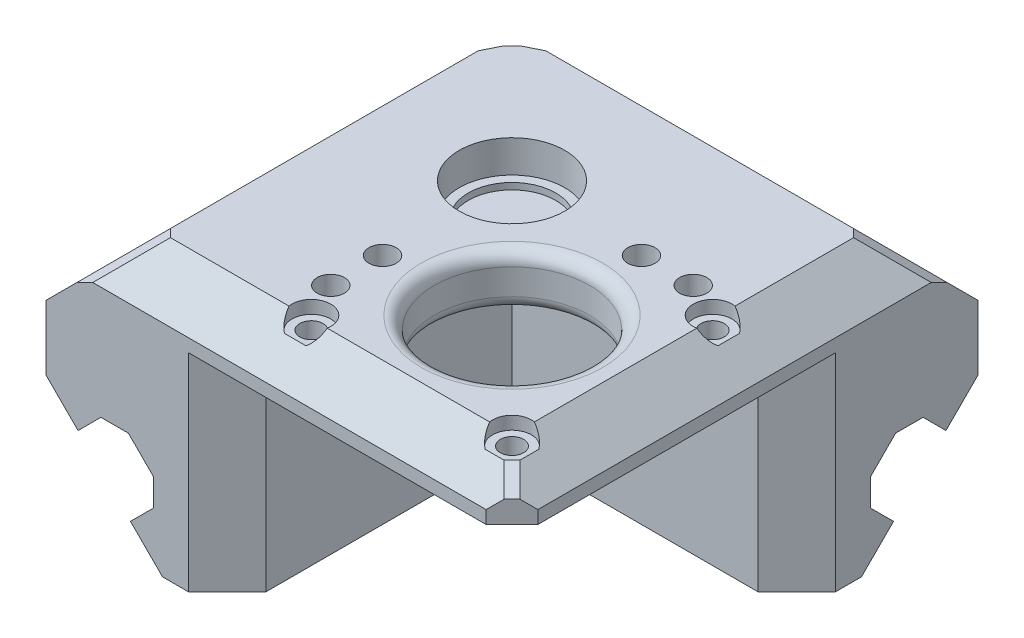
SolidWorks part; units mm, degrees
ref_plane "Front Plane" through (0, 0, 0) normal (0, 0, 1) x (1, 0, 0)
ref_plane "Top Plane" through (0, 0, 0) normal (0, 1, 0) x (1, 0, 0)
ref_plane "Right Plane" through (0, 0, 0) normal (1, 0, 0) x (0, 0, -1)
sketch "Sketch1" plane through (0, 0, 0) normal (0, 1, 0) x (1, 0, 0)
  line L1 (-36, 36) -> (36, 36)
  line L2 (-36, 36) -> (-36, -36)
  line L3 (-36, -36) -> (36, -36)
  line L4 (36, 36) -> (36, -36)
  line L5 (-36, 36) -> (36, -36) construction
  line L6 (-36, -36) -> (36, 36) construction
  circle A0 centre (14, -14) radius 12
  circle A1 centre (29.5, 1.5) radius 1.8
  circle A2 centre (29.5, -29.5) radius 1.8
  circle A3 centre (-1.5, -29.5) radius 1.8
  circle A4 centre (-1.5, 1.5) radius 1.8
  point P0 (0, 0)
  dimension "D3" = 24
  dimension "D5" = 3.6
  dimension "D1" = 72
  dimension "D2" = 72
  dimension "D4" = 22
  dimension "D6" = 31
  dimension "D7" = 15.5
extrude "Boss-Extrude1" add sketch "Sketch1" along normal blind 40
sketch "Sketch6" plane through (0, 0, 0) normal (0, -1, 0) x (-1, 0, 0)
  line L1 (-36, -36) -> (8, -36)
  line L2 (-36, -36) -> (-36, 8)
  line L3 (-36, 8) -> (8, 8)
  line L4 (8, -36) -> (8, 8)
  dimension "D1" = 44
  dimension "D2" = 44
extrude "Cut-Extrude1" cut sketch "Sketch6" against normal blind 32
chamfer "Chamfer1" distance 18 angle 45 3 edges at (-36, 20, -36) (0, 0, -36) (-36, 0, 0)
sketch "Sketch7" plane through (0, 40, 0) normal (0, 1, 0) x (1, 0, 0)
  line L1 (-18, 36) -> (-36, 36)
  line L2 (-18, 36) -> (-18, 18)
  line L3 (-18, 18) -> (-36, 18)
  line L4 (-36, 36) -> (-36, 18)
extrude "Cut-Extrude2" cut sketch "Sketch7" against normal through all
chamfer "Chamfer2" distance 8 angle 45 1 edges at (-18, 20, -18)
chamfer "Chamfer3" distance 4 angle 45 1 edges at (36, 36, 36)
sketch "Sketch8" plane through (0, 40, 0) normal (0, 1, 0) x (1, 0, 0)
  circle A0 centre (-1.5, 1.5) radius 3
  circle A1 centre (29.5, 1.5) radius 3
  circle A2 centre (29.5, -29.5) radius 3
  circle A3 centre (-1.5, -29.5) radius 3
  dimension "D1" = 6
extrude "Cut-Extrude3" cut sketch "Sketch8" against normal blind 2
chamfer "Chamfer5" distance 6 angle 45 2 edges at (36, 16, -8) (-8, 16, 36)
chamfer "Chamfer6" distance 6 angle 45 2 edges at (36, 40, -2) (-2, 40, 36)
chamfer "Chamfer7" distance 12 angle 45 2 edges at (6, 40, -36) (-36, 40, 6)
sketch "Sketch9" plane through (0, -9, -9) normal (0, -0.7071, -0.7071) x (-1, 0, 0)
  circle A0 centre (11.9774, 15.4558) radius 2.1
  circle A1 centre (-20.0226, 15.4558) radius 2.1
  circle A2 centre (-20.0226, 35.4558) radius 2.1
  circle A3 centre (11.9774, 35.4558) radius 2.1
  dimension "D1" = 4.2
extrude "Cut-Extrude4" cut sketch "Sketch9" against normal blind 6
sketch "Sketch10" plane through (-9, -9, 0) normal (-0.7071, -0.7071, 0) x (-0.7071, 0.7071, 0)
  circle A0 centre (35.4558, 12) radius 2.1
  circle A1 centre (35.4558, -20) radius 2.1
  circle A2 centre (15.4558, -20) radius 2.1
  circle A3 centre (15.4558, 12) radius 2.1
  dimension "D1" = 4.2
  dimension "D2" = 32
extrude "Cut-Extrude5" cut sketch "Sketch10" against normal blind 6
sketch "Sketch11" plane through (0, 40, 0) normal (0, 1, 0) x (1, 0, 0)
  line L0 (-18, 36) -> (36, 36) construction
  line L1 (-36, -36) -> (-36, 18) construction
  circle A0 centre (-4, 4) radius 8.15
  dimension "D1" = 16.3
  dimension "D2" = 32
  dimension "D3" = 32
extrude "Cut-Extrude6" cut sketch "Sketch11" against normal blind 5
fillet "Fillet1" radius 2 2 edges at (14, 32, 26) (14, 40, 26)
sketch "Sketch13" plane through (0, 35, 0) normal (0, 1, 0) x (1, 0, 0)
  circle A0 centre (-4, 4) radius 6.75
  dimension "D1" = 13.5
extrude "Cut-Extrude7" cut sketch "Sketch13" against normal blind 1
sketch "Sketch15" plane through (0, 40, 0) normal (0, 1, 0) x (1, 0, 0)
  circle A1 centre (16, 4) radius 2.1
  circle A2 centre (24, 4) radius 2.1
  circle A3 centre (-4, -16) radius 2.1
  circle A4 centre (-4, -24) radius 2.1
  dimension "D1" = 4.2
  dimension "D2" = 52
  dimension "D3" = 32
  dimension "D4" = 32
  dimension "D5" = 52
  dimension "D6" = 8
  dimension "D7" = 8
extrude "Cut-Extrude8" cut sketch "Sketch15" against normal blind 6
chamfer "Chamfer8" distance 1 distance2 1 5 edges at (-25, 39, -19) (-19, 39, -25) (33, 37, -27) (32.8107, 37.1893, 32.8107) (-27, 37, 33)
sketch "Sketch16" plane through (-9, -9, 0) normal (-0.7071, -0.7071, 0) x (-0.7071, 0.7071, 0)
  line L0 (38.1838, -36) -> (12.7279, -36) construction
  line L1 (31.1838, -36) -> (19.7279, -36)
  line L2 (31.1838, -36) -> (31.1838, 40.5684)
  line L3 (31.1838, 40.5684) -> (19.7279, 40.5684)
  line L4 (19.7279, -36) -> (19.7279, 40.5684)
  dimension "D1" = 7
  dimension "D2" = 7
extrude "Cut-Extrude9" cut sketch "Sketch16" against normal blind 8
sketch "Sketch17" plane through (0, -9, -9) normal (0, -0.7071, -0.7071) x (-1, 0, 0)
  line L0 (-36, 12.7279) -> (-36, 38.1838) construction
  line L1 (-36, 19.7279) -> (50.0013, 19.7279)
  line L2 (-36, 19.7279) -> (-36, 31.1838)
  line L3 (-36, 31.1838) -> (50.0013, 31.1838)
  line L4 (50.0013, 19.7279) -> (50.0013, 31.1838)
  dimension "D1" = 7
  dimension "D2" = 7
extrude "Cut-Extrude10" cut sketch "Sketch17" against normal blind 8
chamfer "Chamfer9" distance 3 angle 45 4 edges at (8.6967, 18.7071, -25.3934) (-25.3934, 18.7071, 8.6967) (9.3536, 10.6066, -17.2929) (-17.2929, 10.6066, 9.3536)
